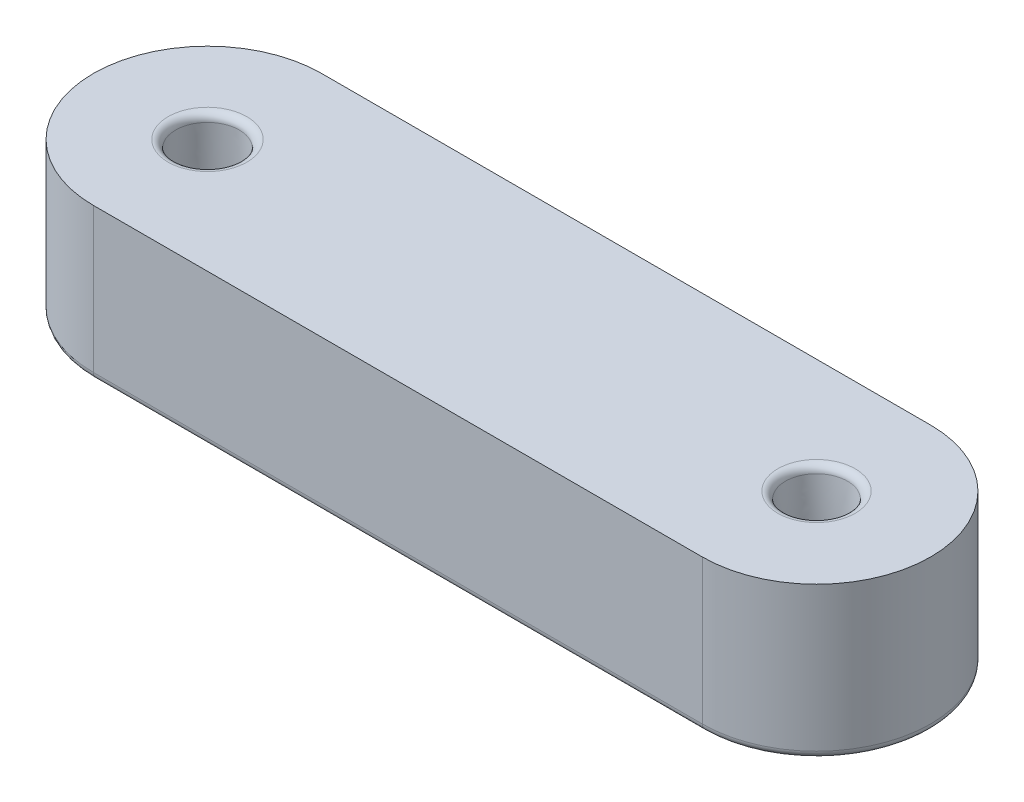
SolidWorks part; units mm, degrees
ref_plane "Front Plane" through (0, 0, 0) normal (0, 0, 1) x (1, 0, 0)
ref_plane "Top Plane" through (0, 0, 0) normal (0, 1, 0) x (1, 0, 0)
ref_plane "Right Plane" through (0, 0, 0) normal (1, 0, 0) x (0, 0, -1)
sketch "Sketch1" plane through (0, 0, 0) normal (0, 1, 0) x (1, 0, 0)
  line L0 (0, 0) -> (20, 0) construction
  line L1 (0, 3.75) -> (20, 3.75)
  line L2 (0, -3.75) -> (20, -3.75)
  arc A0 (0, 3.75) -> (0, -3.75) centre (0, 0) ccw
  arc A2 (20, -3.75) -> (20, 3.75) centre (20, 0) ccw
  arc A3 (16.25, 0) -> (20, -3.75) centre (20, 0) ccw construction
  arc A4 (20, 3.75) -> (16.25, 0) centre (20, 0) ccw construction
  arc A5 (3.75, 0) -> (0, 3.75) centre (0, 0) ccw construction
  arc A6 (0, -3.75) -> (3.75, 0) centre (0, 0) ccw construction
  dimension "D1" = 7.5
  dimension "D2" = 20
extrude "Boss-Extrude1" add sketch "Sketch1" along normal blind 5
sketch "Sketch2" plane through (0, 5, 0) normal (0, 1, 0) x (1, 0, 0)
  circle A0 centre (0, 0) radius 1.04
  circle A1 centre (20, 0) radius 1.04
  dimension "D1" = 2.08
sketch "Sketch3" plane through (0, 0, 0) normal (0, -1, 0) x (1, 0, 0)
  circle A0 centre (0, 0) radius 1.2
  circle A1 centre (20, 0) radius 1.2
  dimension "D1" = 2.4
loft "Cut-Loft1" cut section "Sketch2" section "Sketch3" connector at (19.9458, 5, 1.0386) connector at (21.0099, 0, 0.6481)
loft "Cut-Loft2" cut section "Sketch2<4>" section "Sketch3<4>" connector at (0.5238, 5, 0.8985) connector at (0.9265, 0, 0.7626)
sketch "Sketch2<4>" plane through (0, 5, 0) normal (0, 1, 0) x (1, 0, 0) same geometry as "Sketch2"
sketch "Sketch3<4>" plane through (0, 0, 0) normal (0, -1, 0) x (1, 0, 0) same geometry as "Sketch3"
fillet "Fillet1" radius 0.25 8 edges at (0, 5, 1.04) (0, 0, -1.2) (20, 0, -1.2) (20, 5, 1.04) (23.75, 0, 0) (10, 0, 3.75) (-3.75, 0, 0) (10, 0, -3.75)
